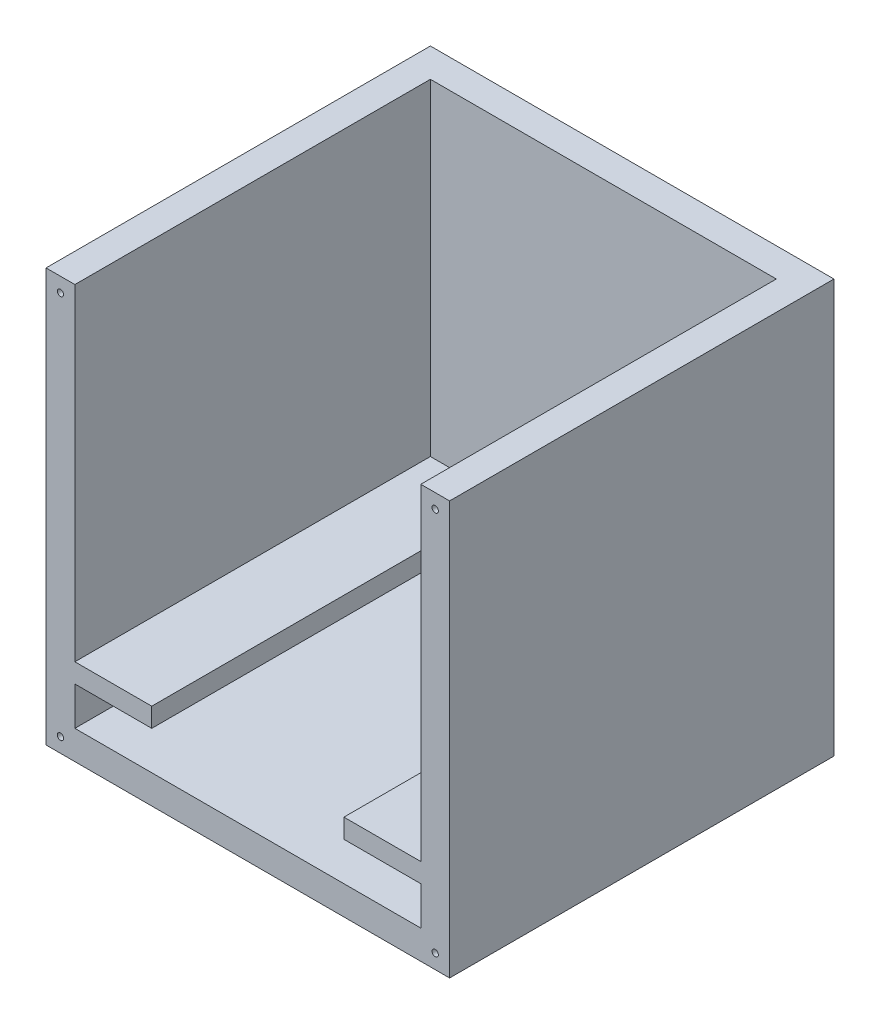
SolidWorks part; units mm, degrees
ref_plane "Front Plane" through (0, 0, 0) normal (0, 0, 1) x (1, 0, 0)
ref_plane "Top Plane" through (0, 0, 0) normal (0, 1, 0) x (1, 0, 0)
ref_plane "Right Plane" through (0, 0, 0) normal (1, 0, 0) x (0, 0, -1)
sketch "Sketch2" plane through (0, 0, 0) normal (0, 1, 0) x (1, 0, 0)
  line L0 (-90, 0) -> (90, 0)
  line L1 (90, 0) -> (90, -185)
  line L2 (-90, 0) -> (-90, -185)
  line L3 (-90, -185) -> (-105, -185)
  line L4 (-105, -185) -> (-105, 15)
  line L5 (-105, 15) -> (105, 15)
  line L6 (105, 15) -> (105, -185)
  line L7 (105, -185) -> (90, -185)
  dimension "D1" = 180
  dimension "D2" = 185
  dimension "D3" = 15
  dimension "D4" = 15
extrude "Boss-Extrude1" add sketch "Sketch2" along normal blind 200
ref_plane "Plane1" through (0, 30, 0) normal (0, 1, 0) x (1, 0, 0)
sketch "Sketch3" plane through (0, 30, 0) normal (0, 1, 0) x (1, 0, 0)
  line L0 (-90, -185) -> (-50, -185)
  line L1 (-50, -185) -> (-50, -10)
  line L2 (-50, -10) -> (50, -10)
  line L3 (50, -10) -> (50, -185)
  line L4 (50, -185) -> (90, -185)
  line L5 (-90, 0) -> (90, 0) construction
  line L14 (-90, -185) -> (-90, 0)
  line L15 (-90, 0) -> (90, 0)
  line L16 (90, 0) -> (90, -185)
  line L17 (90, -185) -> (105, -185)
  line L18 (105, -185) -> (105, 15)
  line L19 (105, 15) -> (-105, 15)
  line L20 (-105, 15) -> (-105, -185)
  line L21 (-105, -185) -> (-90, -185)
  line L22 (-90, -185) -> (-90, 0)
  line L23 (-90, 0) -> (90, 0)
  line L24 (90, 0) -> (90, -185)
  dimension "D1" = 40
  dimension "D2" = 10
  dimension "D3" = 0
extrude "Boss-Extrude2" add sketch "Sketch3" against normal blind 10
sketch "Sketch6" plane through (0, 0, 0) normal (0, -1, 0) x (1, 0, 0)
  line L1 (-105, 185) -> (105, 185)
  line L2 (-105, 185) -> (-105, -15)
  line L3 (-105, -15) -> (105, -15)
  line L4 (105, 185) -> (105, -15)
extrude "Boss-Extrude3" add sketch "Sketch6" along normal blind 15
sketch "Sketch7" plane through (0, 0, -15) normal (0, 0, -1) x (-1, 0, 0)
  line L0 (-105, 200) -> (-105, -15) construction
  line L1 (-90, 20) -> (-47.75, 20)
  line L2 (-90, 20) -> (-90, 0)
  line L3 (-90, 0) -> (-47.75, 0)
  line L4 (-47.75, 20) -> (-47.75, 0)
  line L5 (105, -15) -> (-105, -15) construction
  line L7 (0, -1000) -> (0, 49000) construction
  line L8 (90, 0) -> (47.75, 0)
  line L9 (47.75, 20) -> (47.75, 0)
  line L10 (90, 20) -> (47.75, 20)
  line L11 (90, 20) -> (90, 0)
  dimension "D1" = 15
  dimension "D2" = 15
  dimension "D3" = 42.25
  dimension "D4" = 20
extrude "Cut-Extrude2" cut sketch "Sketch7" against normal up to surface (15 mm away) up to face at (0, 10, 0)
sketch "Sketch5" plane through (0, 0, 185) normal (0, 0, 1) x (1, 0, 0)
  line L0 (-105, 200) -> (-90, 200) construction
  line L1 (-105, 200) -> (-105, -15) construction
  line L2 (0, 0) -> (0, 50000) construction
  line L4 (105, -15) -> (-105, -15) construction
  circle A0 centre (-97.5, 192.5) radius 1.65
  circle A1 centre (97.5, 192.5) radius 1.65
  circle A2 centre (-97.5, -7.5) radius 1.65
  circle A3 centre (97.5, -7.5) radius 1.65
  point P4 (-97.5, 200)
  dimension "D1" = 3.3
  dimension "D4" = 3.3
  dimension "D2" = 7.5
  dimension "D3" = 7.5
  dimension "D5" = 7.5
  dimension "D6" = 7.5
extrude "Cut-Extrude1" cut sketch "Sketch5" against normal blind 10 contours A2 | A1 | A0 | A3
